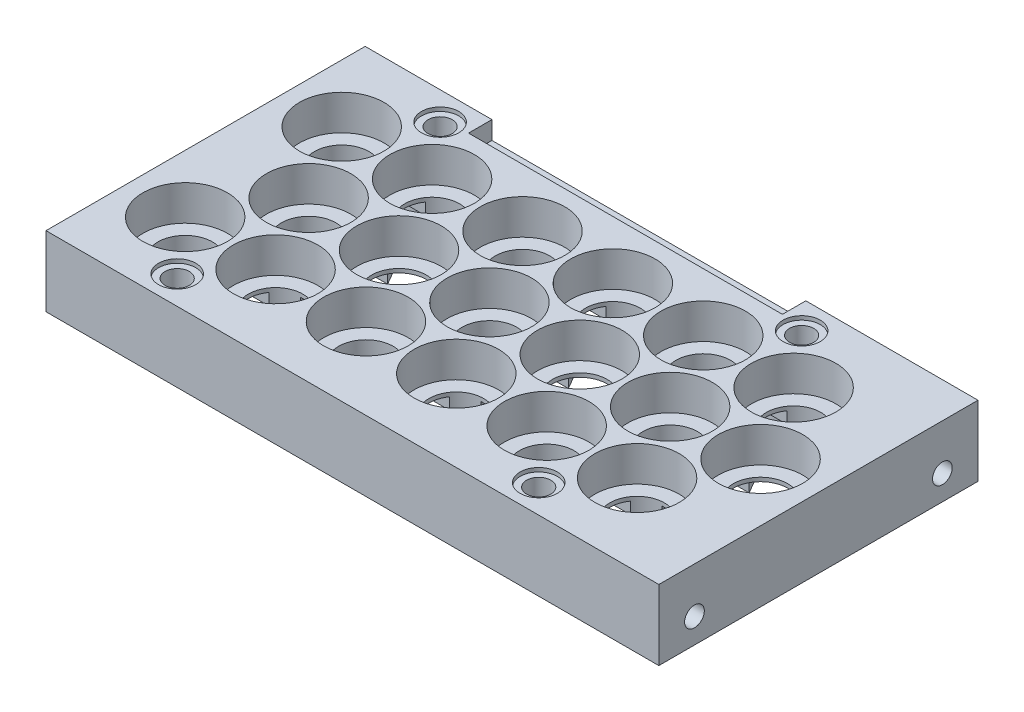
SolidWorks part; units mm, degrees
ref_plane "Front Plane" through (0, 0, 0) normal (0, 0, 1) x (1, 0, 0)
ref_plane "Top Plane" through (0, 0, 0) normal (0, 1, 0) x (1, 0, 0)
ref_plane "Right Plane" through (0, 0, 0) normal (1, 0, 0) x (0, 0, -1)
sketch "Sketch1" plane through (0, 0, 0) normal (0, 1, 0) x (1, 0, 0)
  line L0 (0, 0) -> (11.575, -20.0485) construction
  line L1 (11.575, -20.0485) -> (0, -40.097) construction
  line L2 (0, 0) -> (11.575, 0) construction
  line L3 (11.575, 0) -> (11.575, -20.0485) construction
  line L4 (11.575, -20.0485) -> (11.575, -40.097) construction
  line L5 (11.575, -40.097) -> (0, -40.097) construction
  line L6 (0, 0) -> (23.15, 0) construction
  line L7 (0, 0) -> (23.15, 0) construction
  line L8 (-14.825, -60.922) -> (142.15, -60.922)
  line L9 (-14.825, -60.922) -> (-14.825, 20.825)
  line L10 (-14.825, 20.825) -> (142.15, 20.825)
  line L11 (142.15, -60.922) -> (142.15, 20.825)
  circle A0 centre (0, 0) radius 10.825
  circle A1 centre (11.575, -20.0485) radius 10.825
  circle A2 centre (0, -40.097) radius 10.825
  circle A3 centre (23.15, 0) radius 10.825
  circle A4 centre (34.725, -20.0485) radius 10.825
  circle A5 centre (23.15, -40.097) radius 10.825
  circle A6 centre (46.3, 0) radius 10.825
  circle A7 centre (57.875, -20.0485) radius 10.825
  circle A8 centre (46.3, -40.097) radius 10.825
  circle A9 centre (69.45, 0) radius 10.825
  circle A10 centre (81.025, -20.0485) radius 10.825
  circle A11 centre (69.45, -40.097) radius 10.825
  circle A12 centre (92.6, 0) radius 10.825
  circle A13 centre (104.175, -20.0485) radius 10.825
  circle A14 centre (92.6, -40.097) radius 10.825
  circle A15 centre (115.75, 0) radius 10.825
  circle A16 centre (127.325, -20.0485) radius 10.825
  circle A17 centre (115.75, -40.097) radius 10.825
  circle A18 centre (0, 0) radius 7
  circle A19 centre (11.575, -20.0485) radius 7
  circle A20 centre (0, -40.097) radius 7
  circle A21 centre (23.15, 0) radius 7
  circle A22 centre (34.725, -20.0485) radius 7
  circle A23 centre (23.15, -40.097) radius 7
  circle A24 centre (46.3, 0) radius 7
  circle A25 centre (57.875, -20.0485) radius 7
  circle A26 centre (46.3, -40.097) radius 7
  circle A27 centre (69.45, 0) radius 7
  circle A28 centre (81.025, -20.0485) radius 7
  circle A29 centre (69.45, -40.097) radius 7
  circle A30 centre (92.6, 0) radius 7
  circle A31 centre (104.175, -20.0485) radius 7
  circle A32 centre (92.6, -40.097) radius 7
  circle A33 centre (115.75, 0) radius 7
  circle A34 centre (127.325, -20.0485) radius 7
  circle A35 centre (115.75, -40.097) radius 7
  dimension "D3" = 21.65
  dimension "D11" = 14
  dimension "D1" = 60
  dimension "D2" = 60
  dimension "D4" = 1.5
  dimension "D6" = 23.15
  dimension "D7" = 4
  dimension "D8" = 4
  dimension "D9" = 10
  dimension "D10" = 10
  dimension "D13" = 23.15
  dimension "D12" = 6
extrude "Boss-Extrude2" add sketch "Sketch1" along normal blind 11 and the other way blind 2 contours L8 L11 L10 L9 A17 A16 A15 A14 A13 A12 A11 A10 A9 A8 A7 A6 A5 A4 A3 A2 A1 A0 region at (-13.0551, 0, 20.0485)
extrude "Boss-Extrude3" add sketch "Sketch1<3>" along normal blind 2 and the other way up to surface (2 mm away) contours A0 A18 | A3 A21 | A6 A24 | A9 A27 | A12 A30 | A15 A33 | A1 A19 | A4 A22 | A7 A25 | A10 A28 | A13 A31 | A16 A34 | A17 A35 | A14 A32 | A11 A29 | A8 A26 | A5 A23 | A2 A20 region at (-10.5188, 0, 0) region at (1.0562, 0, 20.0485) region at (-10.5188, 0, 40.097) region at (12.6312, 0, 0) region at (24.2062, 0, 20.0485) region at (12.6312, 0, 40.097) region at (35.7812, 0, 0) region at (47.3562, 0, 20.0485) region at (35.7812, 0, 40.097) region at (58.9312, 0, 0) region at (70.5062, 0, 20.0485) region at (58.9312, 0, 40.097) region at (82.0812, 0, 0) region at (93.6562, 0, 20.0485) region at (82.0812, 0, 40.097) region at (105.2312, 0, 0) region at (116.8062, 0, 20.0485) region at (105.2312, 0, 40.097) other way up to face at (115.75, -2, 50.922)
sketch "Sketch1<3>" plane through (0, 0, 0) normal (0, 1, 0) x (1, 0, 0) same geometry as "Sketch1"
sketch "Sketch2" plane through (0, -2, 0) normal (0, -1, 0) x (1, 0, 0)
  line L0 (0, 40.097) -> (11.575, 20.0485) construction
  line L1 (3.4641, 42.097) -> (15.0391, 22.0485)
  line L2 (-3.4641, 38.097) -> (8.1109, 18.0485)
  line L3 (11.575, 20.0485) -> (0, 0) construction
  line L4 (15.0391, 18.0485) -> (3.4641, -2)
  line L5 (8.1109, 22.0485) -> (-3.4641, 2)
  line L6 (19.6859, 38.097) -> (31.2609, 18.0485)
  line L7 (26.6141, 42.097) -> (38.1891, 22.0485)
  line L8 (31.2609, 22.0485) -> (19.6859, 2)
  line L9 (38.1891, 18.0485) -> (26.6141, -2)
  line L10 (23.15, 40.097) -> (34.725, 20.0485) construction
  line L11 (34.725, 20.0485) -> (23.15, 0) construction
  line L12 (42.8359, 38.097) -> (54.4109, 18.0485)
  line L13 (49.7641, 42.097) -> (61.3391, 22.0485)
  line L14 (54.4109, 22.0485) -> (42.8359, 2)
  line L15 (61.3391, 18.0485) -> (49.7641, -2)
  line L16 (46.3, 40.097) -> (57.875, 20.0485) construction
  line L17 (57.875, 20.0485) -> (46.3, 0) construction
  line L18 (65.9859, 38.097) -> (77.5609, 18.0485)
  line L19 (72.9141, 42.097) -> (84.4891, 22.0485)
  line L20 (77.5609, 22.0485) -> (65.9859, 2)
  line L21 (84.4891, 18.0485) -> (72.9141, -2)
  line L22 (69.45, 40.097) -> (81.025, 20.0485) construction
  line L23 (81.025, 20.0485) -> (69.45, 0) construction
  line L24 (89.1359, 38.097) -> (100.7109, 18.0485)
  line L25 (96.0641, 42.097) -> (107.6391, 22.0485)
  line L26 (100.7109, 22.0485) -> (89.1359, 2)
  line L27 (107.6391, 18.0485) -> (96.0641, -2)
  line L28 (92.6, 40.097) -> (104.175, 20.0485) construction
  line L29 (104.175, 20.0485) -> (92.6, 0) construction
  line L30 (112.2859, 38.097) -> (123.8609, 18.0485)
  line L31 (119.2141, 42.097) -> (130.7891, 22.0485)
  line L32 (123.8609, 22.0485) -> (112.2859, 2)
  line L33 (130.7891, 18.0485) -> (119.2141, -2)
  line L34 (115.75, 40.097) -> (127.325, 20.0485) construction
  line L35 (127.325, 20.0485) -> (115.75, 0) construction
  line L36 (-3.4641, 38.097) -> (19.6859, 38.097) construction
  line L37 (0, 40.097) -> (115.75, 40.097) construction
  line L38 (0, 44.097) -> (115.75, 44.097)
  line L39 (0, 36.097) -> (115.75, 36.097)
  line L40 (11.575, 20.0485) -> (127.325, 20.0485) construction
  line L41 (11.575, 24.0485) -> (127.325, 24.0485)
  line L42 (11.575, 16.0485) -> (127.325, 16.0485)
  line L43 (0, 0) -> (115.75, 0) construction
  line L44 (0, 4) -> (115.75, 4)
  line L45 (0, -4) -> (115.75, -4)
  arc A0 (3.4641, 42.097) -> (-3.4641, 38.097) centre (0, 40.097) ccw
  arc A1 (8.1109, 18.0485) -> (15.0391, 22.0485) centre (11.575, 20.0485) ccw
  arc A2 (15.0391, 18.0485) -> (8.1109, 22.0485) centre (11.575, 20.0485) ccw
  arc A3 (-3.4641, 2) -> (3.4641, -2) centre (0, 0) ccw
  arc A4 (26.6141, 42.097) -> (19.6859, 38.097) centre (23.15, 40.097) ccw
  arc A5 (31.2609, 18.0485) -> (38.1891, 22.0485) centre (34.725, 20.0485) ccw
  arc A6 (38.1891, 18.0485) -> (31.2609, 22.0485) centre (34.725, 20.0485) ccw
  arc A7 (19.6859, 2) -> (26.6141, -2) centre (23.15, 0) ccw
  arc A8 (49.7641, 42.097) -> (42.8359, 38.097) centre (46.3, 40.097) ccw
  arc A9 (54.4109, 18.0485) -> (61.3391, 22.0485) centre (57.875, 20.0485) ccw
  arc A10 (61.3391, 18.0485) -> (54.4109, 22.0485) centre (57.875, 20.0485) ccw
  arc A11 (42.8359, 2) -> (49.7641, -2) centre (46.3, 0) ccw
  arc A12 (72.9141, 42.097) -> (65.9859, 38.097) centre (69.45, 40.097) ccw
  arc A13 (77.5609, 18.0485) -> (84.4891, 22.0485) centre (81.025, 20.0485) ccw
  arc A14 (84.4891, 18.0485) -> (77.5609, 22.0485) centre (81.025, 20.0485) ccw
  arc A15 (65.9859, 2) -> (72.9141, -2) centre (69.45, 0) ccw
  arc A16 (96.0641, 42.097) -> (89.1359, 38.097) centre (92.6, 40.097) ccw
  arc A17 (100.7109, 18.0485) -> (107.6391, 22.0485) centre (104.175, 20.0485) ccw
  arc A18 (107.6391, 18.0485) -> (100.7109, 22.0485) centre (104.175, 20.0485) ccw
  arc A19 (89.1359, 2) -> (96.0641, -2) centre (92.6, 0) ccw
  arc A20 (119.2141, 42.097) -> (112.2859, 38.097) centre (115.75, 40.097) ccw
  arc A21 (123.8609, 18.0485) -> (130.7891, 22.0485) centre (127.325, 20.0485) ccw
  arc A22 (130.7891, 18.0485) -> (123.8609, 22.0485) centre (127.325, 20.0485) ccw
  arc A23 (112.2859, 2) -> (119.2141, -2) centre (115.75, 0) ccw
  arc A24 (0, 44.097) -> (0, 36.097) centre (0, 40.097) ccw
  arc A25 (115.75, 36.097) -> (115.75, 44.097) centre (115.75, 40.097) ccw
  arc A26 (11.575, 24.0485) -> (11.575, 16.0485) centre (11.575, 20.0485) ccw
  arc A27 (127.325, 16.0485) -> (127.325, 24.0485) centre (127.325, 20.0485) ccw
  arc A28 (0, 4) -> (0, -4) centre (0, 0) ccw
  arc A29 (115.75, -4) -> (115.75, 4) centre (115.75, 0) ccw
  point P3 (5.7875, 30.0727)
  point P8 (5.7875, 10.0242)
  point P18 (28.9375, 30.0727)
  point P25 (28.9375, 10.0242)
  point P34 (52.0875, 30.0727)
  point P39 (52.0875, 10.0242)
  point P48 (75.2375, 30.0727)
  point P53 (75.2375, 10.0242)
  point P62 (98.3875, 30.0727)
  point P67 (98.3875, 10.0242)
  point P76 (121.5375, 30.0727)
  point P81 (121.5375, 10.0242)
  point P91 (57.875, 40.097)
  point P96 (69.45, 20.0485)
  point P103 (57.875, 0)
  circle M99 centre (0, 0) radius 7
  circle M100 centre (23.15, 0) radius 7
  circle M101 centre (46.3, 0) radius 7
  circle M102 centre (69.45, 0) radius 7
  circle M103 centre (92.6, 0) radius 7
  circle M104 centre (115.75, 0) radius 7
  circle M105 centre (11.575, 20.0485) radius 7
  circle M106 centre (34.725, 20.0485) radius 7
  circle M107 centre (57.875, 20.0485) radius 7
  circle M108 centre (81.025, 20.0485) radius 7
  circle M109 centre (104.175, 20.0485) radius 7
  circle M110 centre (127.325, 20.0485) radius 7
  circle M111 centre (115.75, 40.097) radius 7
  circle M112 centre (92.6, 40.097) radius 7
  circle M113 centre (69.45, 40.097) radius 7
  circle M114 centre (46.3, 40.097) radius 7
  circle M115 centre (23.15, 40.097) radius 7
  circle M116 centre (0, 40.097) radius 7
  dimension "D1" = 8
  dimension "D3" = 23.15
  dimension "D4" = 8
  dimension "D5" = 8
  dimension "D6" = 8
extrude "Cut-Extrude1" cut sketch "Sketch2" against normal blind 3 contours L1 L39 L38 M115 M116 | L6 L41 L7 L39 M106 M115 | L42 L8 L6 L41 M105 M106 | L45 L44 L4 M99 M100 | L44 L9 L42 L8 M100 M106 | L8 L42 M106 | L41 L6 M106 | L39 L1 M116 | L44 L4 M99 | L44 L9 M100 | L42 L20 L18 L41 M107 M108 | L45 L44 L15 M101 M102 | L13 L39 L38 M113 M114 | L18 L41 L19 L39 M108 M113 | L44 L21 L42 L20 M102 M108 | L45 L44 L27 M103 M104 | L42 L32 L30 L41 M109 M110 | L25 L39 L38 M111 M112 | L30 L41 L31 M110 M111 | L42 L32 L33 M104 M110 | L32 L42 M110 | L41 L30 M110 | L44 L27 M103 | L39 L25 M112 | L44 L21 M102 | L39 L19 M113 | L44 L15 M101 | L20 L42 M108 | L41 L18 M108 | L39 L13 M114 | L39 L7 M115 region at (11.6138, -2, 40.1242) region at (6.3461, -2, 36.4331) region at (23.0718, -2, 20.0485) region at (28.9375, -2, 30.0727) region at (28.3789, -2, 23.7124) region at (29.4961, -2, 36.4331) region at (57.9138, -2, 40.1242) region at (28.3789, -2, 16.3846) region at (28.9375, -2, 10.0242) region at (6.3461, -2, 3.6639) region at (11.6138, -2, -0.0272) region at (52.6461, -2, 36.4331) region at (29.4961, -2, 3.6639) region at (75.2375, -2, 30.0727) region at (75.7961, -2, 36.4331) region at (104.2138, -2, 40.1242) region at (74.6789, -2, 23.7124) region at (69.3718, -2, 20.0485) region at (57.9138, -2, -0.0272) region at (98.9461, -2, 36.4331) region at (74.6789, -2, 16.3846) region at (52.6461, -2, 3.6639) region at (121.5416, -2, 30.12) region at (75.2375, -2, 10.0242) region at (120.9789, -2, 23.7124) region at (115.6718, -2, 20.0485) region at (75.7961, -2, 3.6639) region at (104.2138, -2, -0.0272) region at (121.5416, -2, 9.977) region at (120.9789, -2, 16.3846) region at (98.9461, -2, 3.6639)
sketch "Sketch9" plane through (0, 11, 0) normal (0, 1, 0) x (1, 0, 0)
  line L0 (11.575, -60.922) -> (11.575, 20.825)
  line L1 (-14.825, 20.825) -> (142.15, 20.825) construction
  line L2 (104.175, 20.825) -> (104.175, -60.922)
  line L3 (-14.825, -60.922) -> (142.15, -60.922) construction
  circle A0 centre (11.575, 13.625) radius 3.1
  circle A1 centre (11.575, -53.722) radius 3.1
  circle A2 centre (104.175, -53.722) radius 3.1
  circle A3 centre (104.175, 13.625) radius 3.1
  point P0 (11.575, 13.625)
  point P7 (11.575, -20.0485)
  point P15 (104.175, -20.0485)
  point P20 (104.175, 13.625)
  point P21 (104.175, -53.722)
  point P22 (11.575, -53.722)
  dimension "D5" = 6.2
  dimension "D1" = 7.2
  dimension "D4" = 7.2
extrude "Cut-Extrude3" cut sketch "Sketch9" against normal up to next contours A2 | A1 | A0 | A3
sketch "Sketch10" plane through (0, 11, 0) normal (0, 1, 0) x (1, 0, 0)
  circle A0 centre (11.575, 13.625) radius 4.7625
  circle A1 centre (104.175, 13.625) radius 4.7625
  circle A2 centre (104.175, -53.722) radius 4.7625
  circle A3 centre (11.575, -53.722) radius 4.7625
  dimension "D1" = 9.525
extrude "Cut-Extrude4" cut sketch "Sketch10" against normal blind 1
sketch "Sketch13" plane through (0, -2, 0) normal (0, -1, 0) x (1, 0, 0)
  line L0 (142.15, 60.922) -> (142.15, -20.825) construction
  line L5 (3.575, 53.722) -> (3.575, 60.922)
  line L8 (-14.825, 60.922) -> (142.15, 60.922) construction
  line L9 (3.575, 60.922) -> (19.575, 60.922)
  line L10 (19.575, 60.922) -> (19.575, 53.722)
  line L12 (57.875, 20.0485) -> (57.875, -20.825) construction
  line L13 (-14.825, -20.825) -> (142.15, -20.825) construction
  line L14 (11.575, 20.0485) -> (127.325, 20.0485) construction
  line L16 (96.175, 60.922) -> (96.175, 53.722)
  line L17 (112.175, 60.922) -> (96.175, 60.922)
  line L18 (112.175, 53.722) -> (112.175, 60.922)
  line L19 (-14.825, 60.922) -> (142.15, 60.922)
  line L20 (-14.825, 60.922) -> (-14.825, 53.922)
  line L21 (-14.825, 53.922) -> (142.15, 53.922)
  line L22 (142.15, 60.922) -> (142.15, 53.922)
  line L23 (142.15, -20.825) -> (142.15, -13.825)
  line L24 (-14.825, -13.825) -> (142.15, -13.825)
  line L25 (-14.825, -20.825) -> (-14.825, -13.825)
  line L26 (-14.825, -20.825) -> (142.15, -20.825)
  line L27 (112.175, -13.625) -> (112.175, -20.825)
  line L28 (112.175, -20.825) -> (96.175, -20.825)
  line L29 (96.175, -20.825) -> (96.175, -13.625)
  line L32 (19.575, -20.825) -> (19.575, -13.625)
  line L33 (3.575, -20.825) -> (19.575, -20.825)
  line L34 (3.575, -13.625) -> (3.575, -20.825)
  line L35 (137.15, 53.922) -> (125.15, 53.922)
  line L36 (-14.825, 53.922) -> (-9.825, 53.922)
  line L37 (-14.825, 53.922) -> (-14.825, -13.825)
  line L38 (-14.825, -13.825) -> (-9.825, -13.825)
  line L39 (-9.825, 53.922) -> (-9.825, -13.825)
  line L40 (142.15, 53.922) -> (137.15, 53.922)
  line L41 (142.15, 53.922) -> (142.15, -13.825)
  line L42 (142.15, -13.825) -> (137.15, -13.825)
  line L43 (137.15, 53.922) -> (137.15, -13.825)
  line L44 (137.15, 53.922) -> (137.15, 41.922)
  line L45 (125.15, 53.922) -> (125.15, 41.922)
  line L46 (137.15, 41.922) -> (125.15, 41.922)
  line L47 (125.15, 53.922) -> (137.15, 41.922)
  line L48 (137.15, -13.825) -> (125.15, -13.825)
  line L49 (137.15, -13.825) -> (137.15, -1.825)
  line L50 (125.15, -13.825) -> (125.15, -1.825)
  line L51 (137.15, -1.825) -> (125.15, -1.825)
  line L52 (125.15, -13.825) -> (137.15, -1.825)
  circle A4 centre (11.575, 53.722) radius 3.1
  circle A5 centre (11.575, 53.722) radius 8
  circle A6 centre (104.175, 53.722) radius 8
  circle A7 centre (104.175, 53.722) radius 3.1
  circle A8 centre (104.175, -13.625) radius 3.1
  circle A9 centre (104.175, -13.625) radius 8
  circle A10 centre (11.575, -13.625) radius 8
  circle A11 centre (11.575, -13.625) radius 3.1
  circle A12 centre (11.575, 53.722) radius 3.1 construction
  dimension "D2" = 16
  dimension "D3" = 7
  dimension "D1" = 5
  dimension "D4" = 5
  dimension "D6" = 12
extrude "Boss-Extrude7" add sketch "Sketch13" along normal blind 5 contours L21 L5 | A5 L5 L21 | A5 L21 L10 | L10 L21 L16 | L21 A5 L19 A4 | A5 L21 A4 | L21 A6 L16 | L21 A7 A6 L19 | L21 A7 A6 | A6 L21 L18 | L18 L21 | A9 L24 L29 L26 | L28 A9 L24 A8 | A9 L26 L27 L24 | L24 L27 L26 | L32 L26 L29 L24 | L24 A9 A8 | L34 L24 | L26 A10 L24 L34 | L24 A11 A10 | L24 A11 A10 L33 | L24 A10 L26 L32 | L39 L21 L37 L24 | L21 L43 L24 L41 | L52 L24 L43 | L21 L47 L43 region at (11.575, -2, 50.0459) region at (-5.625, -2, 57.422) region at (4.8234, -2, 59.2386) region at (11.575, -2, 57.3976) region at (-12.325, -2, 20.0485) region at (18.3266, -2, 59.2386) region at (57.875, -2, 57.422) region at (-5.625, -2, -17.325) region at (97.4234, -2, 59.2386) region at (4.8234, -2, -19.1416) region at (104.175, -2, 50.0459) region at (104.175, -2, 57.3976) region at (11.575, -2, -9.9489) region at (11.575, -2, -17.3006) region at (110.9266, -2, 59.2386) region at (127.1625, -2, 57.422) region at (18.3266, -2, -19.1416) region at (57.875, -2, -17.325) region at (133.15, -2, 49.922) region at (97.4234, -2, -19.1416) region at (139.65, -2, 20.0485) region at (104.175, -2, -9.9489) region at (104.175, -2, -17.3006) region at (133.15, -2, -9.825) region at (127.1625, -2, -17.325) region at (110.9266, -2, -19.1416)
sketch "Sketch18" plane through (0, 0, -20.825) normal (0, 0, -1) x (-1, 0, 0)
  line L0 (-97.85, 6.575) -> (-17.85, 6.575)
  line L1 (-97.85, 6.575) -> (-97.85, 11)
  line L6 (-17.85, 6.575) -> (-17.85, 11)
  line L8 (-97.85, 11) -> (-17.85, 11)
  line L9 (14.825, 11) -> (-142.15, 11) construction
  line L10 (-17.85, 67.575) -> (-17.85, 6.575) construction
  line L15 (-98.05, 6.375) -> (-17.65, 6.375)
  line L16 (-17.65, 6.375) -> (-17.65, 11.2)
  line L17 (-98.05, 11.2) -> (-17.65, 11.2)
  line L18 (-98.05, 6.375) -> (-98.05, 11.2)
  line M8 (14.825, 11) -> (-142.15, 11)
  dimension "D1" = 0.2
extrude "Cut-Extrude6" cut sketch "Sketch18" against normal blind 6 contours M8 | L18 L15 L16 L6 L0 L1 M8 region at (57.85, 8.7875, -20.825) region at (57.85, 6.4945, -20.825)
sketch "Sketch19" plane through (0, 0, -20.825) normal (0, 0, -1) x (-1, 0, 0)
  line L4 (-57.85, -7) -> (-57.85, 6.375)
  line L5 (-98.05, 6.375) -> (-98.05, 11) construction
  line L6 (-57.85, -7) -> (-57.85, -0.3125)
  line L7 (14.825, -7) -> (-142.15, -7) construction
  line L8 (-98.05, 6.375) -> (-17.65, 6.375) construction
  line L10 (-29.65, -0.3125) -> (-86.05, -0.3125)
  circle A0 centre (-86.05, -0.3125) radius 2.525
  circle A1 centre (-29.65, -0.3125) radius 2.525
  point P8 (-57.85, 6.375)
  point P10 (-57.85, -6.9857)
  point P12 (-87.7932, -0.3125)
  point P13 (-57.85, -0.3125)
  point P14 (-57.85, -0.3125)
  dimension "D2" = 5.05
  dimension "D1" = 12
extrude "Cut-Extrude7" cut sketch "Sketch19" against normal blind 5 contours A0 | A0 | A1 | A1 region at (88.5036, -0.3125, -20.825) region at (29.65, 2.1411, -20.825)
sketch "Sketch20" plane through (142.15, 0, 0) normal (1, 0, 0) x (0, 0, -1)
  circle A0 centre (-51.7985, -0.65) radius 2.525
  circle A1 centre (11.7015, -0.65) radius 2.525
  circle A2 centre (-51.7985, -0.65) radius 2.525 construction
  circle A3 centre (11.7015, -0.65) radius 2.525 construction
  dimension "D1" = 5.05
extrude "Cut-Extrude8" cut sketch "Sketch20" against normal blind 10 contours A0 | A0 | A1 region at (142.15, -0.65, 51.7985)
sketch "Sketch21" plane through (0, -2, 0) normal (0, -1, 0) x (1, 0, 0)
  line L0 (57.875, 44.097) -> (57.875, 53.922) construction
  line L1 (52.0446, 44.097) -> (63.7054, 44.097) construction
  line L2 (19.5725, 53.922) -> (96.1775, 53.922) construction
  line L3 (137.15, 41.922) -> (122.5079, 41.922) construction
  line L5 (57.875, 20.0485) -> (-2.625, 20.0485) construction
  line L6 (4.575, 20.0485) -> (-9.825, 20.0485) construction
  line L7 (-9.825, 53.922) -> (-9.825, -13.825) construction
  line L9 (57.875, -4) -> (57.875, -13.825) construction
  circle A0 centre (57.875, 49.0095) radius 1.9431
  circle A1 centre (129.829, 41.922) radius 1.9431
  circle A3 centre (-2.625, 20.0485) radius 1.9431
  arc A4 (17.3196, 24.0485) -> (17.3196, 16.0485) centre (11.575, 20.0485) ccw construction
  circle A5 centre (129.829, -1.825) radius 1.9431
  circle A6 centre (57.875, -8.9125) radius 1.9431
  arc A8 (122.0864, 37.122) -> (110.0054, 44.097) centre (115.75, 40.097) ccw construction
  point P12 (129.829, 41.922)
  dimension "D1" = 3.8862
extrude "Cut-Extrude9" cut sketch "Sketch21" against normal blind 3.81
equation "\"hole_diameter\"= 21.65"
equation "\"D3@Sketch1\"=\"hole_diameter\""
equation "\"cell_spacing\"= 1.5"
equation "\"D4@Sketch1\"=\"cell_spacing\""
equation "\"D6@Sketch1\"=\"hole_diameter\"+\"cell_spacing\""
equation "\"len_spacing\"= 4"
equation "\"D7@Sketch1\"=\"len_spacing\""
equation "\"D8@Sketch1\"=\"len_spacing\""
equation "\"wid_spacing\"= 10"
equation "\"D9@Sketch1\"=\"wid_spacing\""
equation "\"D10@Sketch1\"=\"wid_spacing\""
equation "\"nipple\"= 14"
equation "\"D11@Sketch1\"=\"nipple\""
equation "\"D13@Sketch1\"=\"hole_diameter\"+\"cell_spacing\""
equation "\"channel\"= 8"
equation "\"D1@Sketch2\"=\"channel\""
equation "\"D3@Sketch2\"=\"hole_diameter\"+\"cell_spacing\""
equation "\"D4@Sketch2\"=\"channel\""
equation "\"D5@Sketch2\"=\"channel\""
equation "\"D6@Sketch2\"=\"channel\""
equation "\"lip\"= 7"
equation "\"lip_height\"= 1"
equation "\"outer_fillet\"=6"
equation "\"insert_placement\"= 7.2"
equation "\"D4@Sketch9\"=\"insert_placement\""
equation "\"D1@Sketch9\"=\"insert_placement\""
equation "\"heat_insert_diameter\"= 5.05"
equation "\"bolt_shaft_diameter\"=6.2"
equation "\"D5@Sketch9\"=\"bolt_shaft_diameter\""
equation "\"heat_insert_lip_diameter\"=9.525"
equation "\"D1@Sketch10\"=\"heat_insert_lip_diameter\""
equation "\"bolt_head_diameter\"=13"
equation "\"D2@Sketch13\"=\"bolt_head_diameter\"+3"
equation "\"D3@Sketch13\"=\"lip\""
equation "\"small_heat_insert\"= .153in"
equation "\"bdm_cut_depth\"=6"
equation "\"D1@Cut-Extrude6\"=\"bdm_cut_depth\""
equation "\"D2@Sketch19\"=\"heat_insert_diameter\""
equation "\"heat_insert_depth\"=3.81"
equation "\"D1@Sketch21\"=\"small_heat_insert\""
equation "\"D1@Sketch20\"=\"heat_insert_diameter\""
equation "\"heat_insert_space\"=6"
equation "\"heat_insert\"=5.5"
